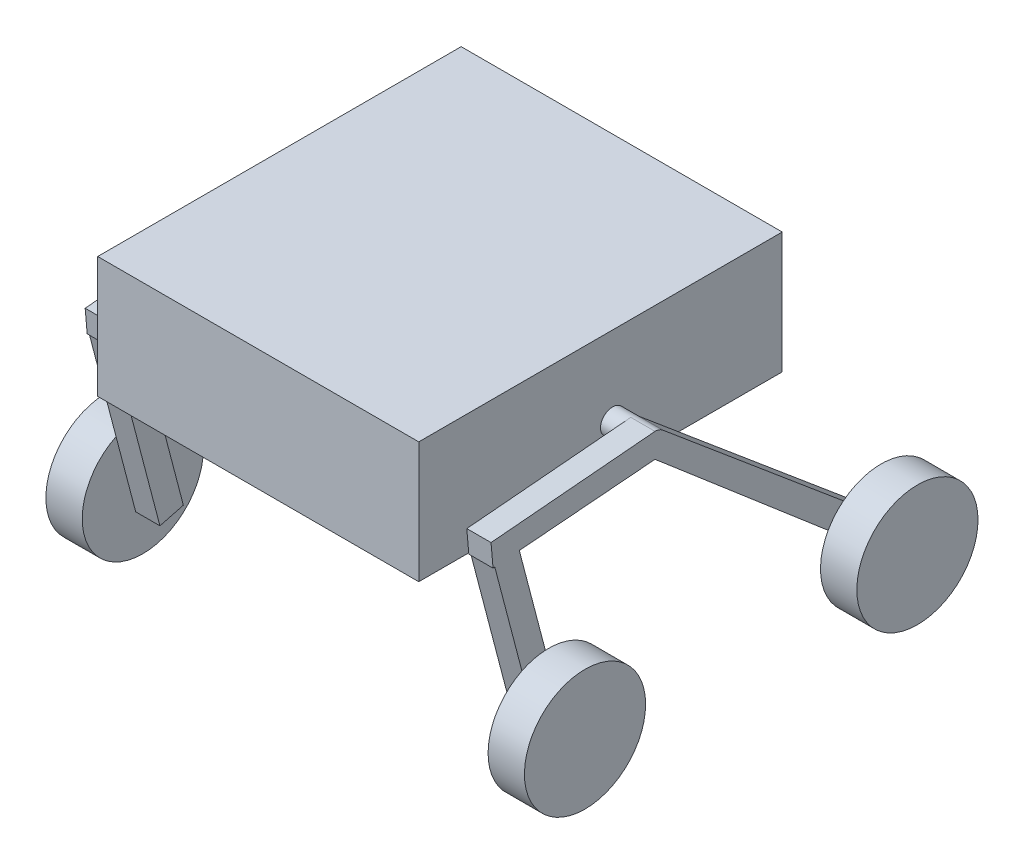
SolidWorks part; units mm, degrees
ref_plane "Front Plane" through (0, 0, 0) normal (0, 0, 1) x (1, 0, 0)
ref_plane "Top Plane" through (0, 0, 0) normal (0, 1, 0) x (1, 0, 0)
ref_plane "Right Plane" through (0, 0, 0) normal (1, 0, 0) x (0, 0, -1)
other "Center of Mass"
sketch "Sketch1" plane through (0, 0, 0) normal (0, 1, 0) x (1, 0, 0)
  line L0 (0, 0) -> (0, 762)
  line L1 (0, 762) -> (673.1, 762)
  line L2 (673.1, 762) -> (673.1, 0)
  line L3 (673.1, 0) -> (0, 0)
extrude "Boss-Extrude1" add sketch "Sketch1" along normal blind 254
sketch "Sketch2" plane through (673.1, 0, 0) normal (1, 0, 0) x (0, 0, -1)
  line L0 (762, 88.9) -> (406.4, 88.9) construction
  line L2 (0, 0) -> (762, 0) construction
  line L3 (762, 254) -> (762, 0) construction
  circle A0 centre (406.4, 88.9) radius 25.4
  dimension "D2" = 355.6
  dimension "D1" = 88.9
extrude "Boss-Extrude2" add sketch "Sketch2" along normal blind 38.1
sketch "Sketch3" plane through (711.2, 0, 0) normal (1, 0, 0) x (0, 0, -1)
  line L9 (406.4, 88.9) -> (909.5288, -333.2752) construction
  line L11 (422.7268, 108.3575) -> (925.8556, -313.8177)
  line L12 (925.8556, -313.8177) -> (909.5288, -333.2752)
  line L13 (909.5288, -333.2752) -> (893.202, -352.7327)
  line L14 (893.202, -352.7327) -> (406.4, 63.5)
  line L16 (406.4, 88.9) -> (0, 88.9) construction
  line L17 (0, 254) -> (0, 0) construction
  line L18 (406.4, 88.9) -> (25.4342, 55.5698) construction
  line L19 (406.4, 88.9) -> (90.1082, 61.2281) construction
  line L20 (64.8048, 59.0143) -> (66.8457, 35.6871)
  line L21 (64.8048, 59.0143) -> (62.5911, 84.3176)
  line L22 (62.5911, 84.3176) -> (406.4, 114.3)
  line L23 (66.8457, 35.6871) -> (70.4653, 35.9836)
  line L26 (90.1082, 61.2281) -> (193.1163, -331.9008) construction
  line L27 (193.1163, -331.9008) -> (217.6868, -325.4628)
  line L28 (193.1163, -331.9008) -> (168.5457, -338.3388)
  line L29 (168.5457, -338.3388) -> (70.4653, 35.9836)
  line L30 (217.6868, -325.4628) -> (121.8768, 40.1947)
  line L31 (121.8768, 40.1947) -> (406.4, 63.5)
  circle A0 centre (406.4, 88.9) radius 25.4 construction
  circle A1 centre (406.4, 88.9) radius 25.4 construction
  arc A2 (406.4, 114.3) -> (422.7268, 108.3575) centre (406.4, 88.9) cw
  dimension "D1" = 80
  dimension "D2" = 135
  dimension "D3" = 5
extrude "Boss-Extrude3" add sketch "Sketch3" along normal blind 50.8
sketch "Sketch4" plane through (762, 0, 0) normal (1, 0, 0) x (0, 0, -1)
  line L0 (193.1163, -331.9008) -> (183.4593, -295.045) construction
  line L1 (168.5457, -338.3388) -> (217.6868, -325.4628) construction
  line L2 (909.5288, -333.2752) -> (880.3425, -308.785) construction
  line L3 (893.202, -352.7327) -> (925.8556, -313.8177) construction
  circle A2 centre (183.4593, -295.045) radius 127
  circle A3 centre (880.3425, -308.785) radius 127
extrude "Boss-Extrude4" add sketch "Sketch4" along normal blind 76.2
ref_plane "Plane1" through (336.55, 0, 0) normal (1, 0, 0) x (0, 0, -1)
mirror "Mirror1" about plane through (336.55, 0, 0) normal (1, 0, 0) of "Boss-Extrude4", "Boss-Extrude3", "Boss-Extrude2"
ref_axis "Axis1" through (762, 88.9, -406.4) along (-1, 0, 0)
